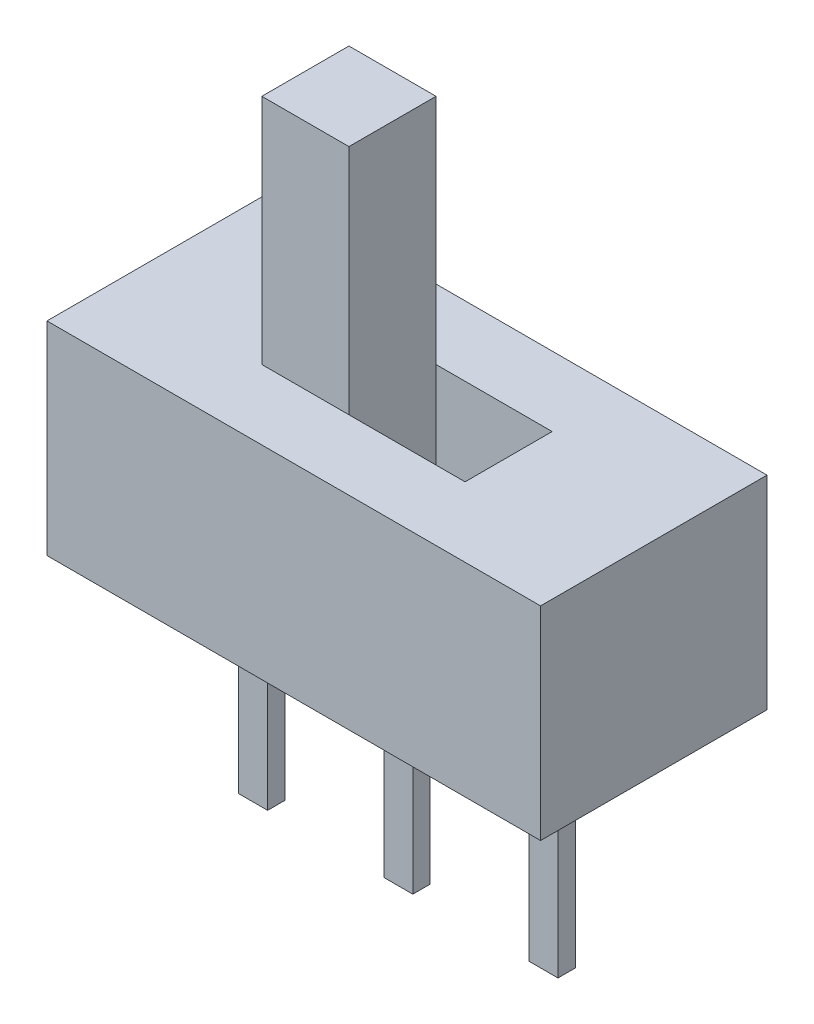
SolidWorks part; units mm, degrees
ref_plane "Front Plane" through (0, 0, 0) normal (0, 0, 1) x (1, 0, 0)
ref_plane "Top Plane" through (0, 0, 0) normal (0, 1, 0) x (1, 0, 0)
ref_plane "Right Plane" through (0, 0, 0) normal (1, 0, 0) x (0, 0, -1)
sketch "Sketch1" plane through (0, 0, 0) normal (0, 1, 0) x (1, 0, 0)
  line L1 (-4.25, 1.95) -> (4.25, 1.95)
  line L2 (-4.25, 1.95) -> (-4.25, -1.95)
  line L3 (-4.25, -1.95) -> (4.25, -1.95)
  line L4 (4.25, 1.95) -> (4.25, -1.95)
  line L5 (0, -1.95) -> (0, 1.95) construction
  line L6 (-4.25, 0) -> (4.25, 0) construction
  point P0 (0, 0)
  dimension "D1" = 8.5
  dimension "D2" = 3.9
extrude "Boss-Extrude1" add sketch "Sketch1" along normal blind 3.5
sketch "Sketch2" plane through (0, 3.5, 0) normal (0, 1, 0) x (1, 0, 0)
  line L0 (0, -2.975) -> (0, 2.975) construction
  line L1 (-1.75, 0.75) -> (1.75, 0.75)
  line L2 (-1.75, 0.75) -> (-1.75, -0.75)
  line L3 (-1.75, -0.75) -> (1.75, -0.75)
  line L4 (1.75, 0.75) -> (1.75, -0.75)
  line L5 (-4.675, 0) -> (4.675, 0) construction
  point P0 (0, 0.75)
  point P6 (-1.75, 0)
  point P9 (0, 0)
  dimension "D1" = 1.5
  dimension "D2" = 3.5
extrude "Cut-Extrude1" cut sketch "Sketch2" against normal blind 2
sketch "Sketch3" plane through (0, 1.5, 0) normal (0, 1, 0) x (1, 0, 0)
  line L0 (-4.675, 0) -> (4.675, 0) construction
  line L5 (-1.75, 0.75) -> (-0.25, 0.75)
  line L6 (-1.75, 0.75) -> (-1.75, -0.75)
  line L7 (-1.75, -0.75) -> (-0.25, -0.75)
  line L8 (-0.25, 0.75) -> (-0.25, -0.75)
  line L9 (-1, -0.75) -> (-1, 0.75) construction
  line L10 (-1.75, 0) -> (-0.25, 0) construction
  point P0 (-1, 0)
  point P6 (0, 0)
  point P7 (-1.75, 0.75)
  point P8 (-1.7077, 0.75)
  point P9 (-1.75, -0.75)
  point P10 (0, 0)
  point P11 (-1.6457, 0.75)
extrude "Boss-Extrude3" add sketch "Sketch3" along normal offset from surface (6 mm away) 4 up to face at (0, 3.5, 0) offset beyond the face yes
sketch "Sketch4" plane through (0, 0, 0) normal (0, -1, 0) x (1, 0, 0)
  line L1 (-0.25, 0.15) -> (0.25, 0.15)
  line L2 (-0.25, 0.15) -> (-0.25, -0.15)
  line L3 (-0.25, -0.15) -> (0.25, -0.15)
  line L4 (0.25, 0.15) -> (0.25, -0.15)
  line L5 (0, -0.15) -> (0, 0.15) construction
  line L6 (-0.25, 0) -> (0.25, 0) construction
  point P0 (0, 0)
  dimension "D1" = 0.5
  dimension "D2" = 0.3
extrude "Boss-Extrude4" add sketch "Sketch4" along normal blind 3.7
pattern_linear "LPattern1" count 2 spacing 2.5 along (1, 0, 0) count 2 spacing 2.5 along (-1, 0, 0) of "Boss-Extrude4" pattern seed only yes
equation "\"D1@Boss-Extrude3\" = 2 + 5.5"
